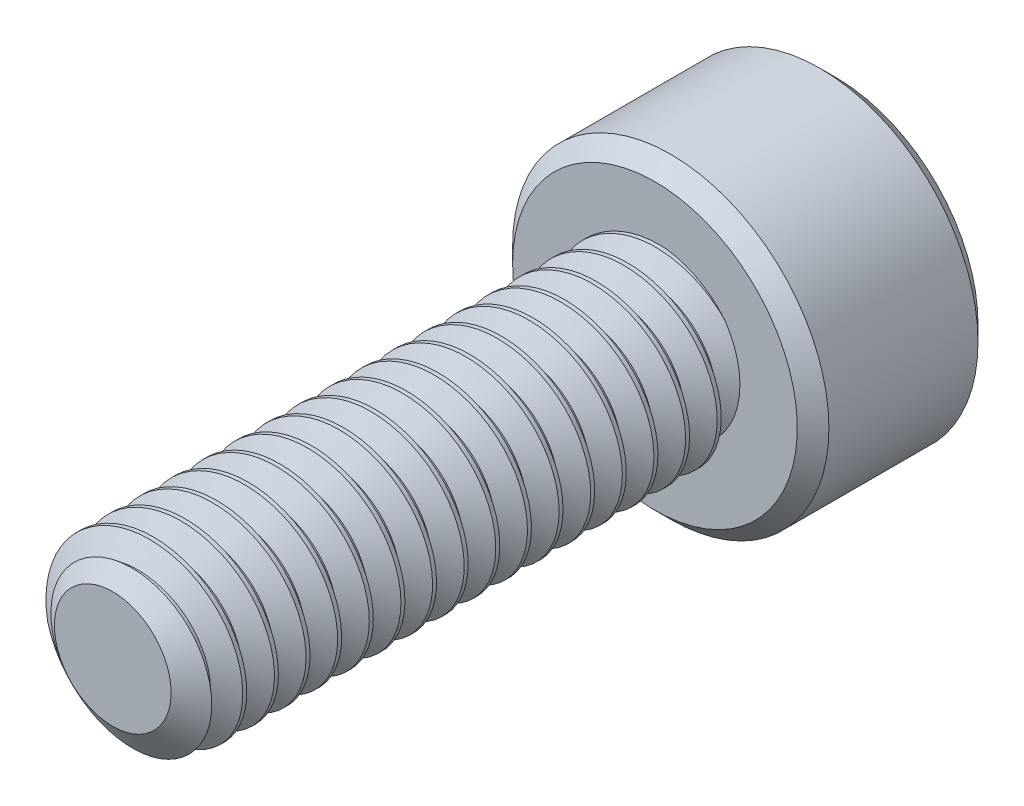
SolidWorks part; units mm, degrees
ref_plane "Front Plane" through (0, 0, 0) normal (0, 0, 1) x (1, 0, 0)
ref_plane "Top Plane" through (0, 0, 0) normal (0, 1, 0) x (1, 0, 0)
ref_plane "Right Plane" through (0, 0, 0) normal (1, 0, 0) x (0, 0, -1)
sketch "Sketch1" plane through (0, 0, 0) normal (0, 0, 1) x (1, 0, 0)
  circle A0 centre (0, 0) radius 2
  dimension "OD" = 4
extrude "Extrude1" add sketch "Sketch1" against normal blind 12
sketch "Sketch2" plane through (0, 0, 0) normal (0, 0, 1) x (1, 0, 0)
  circle A0 centre (0, 0) radius 2 construction
  circle A1 centre (0, 0) radius 2
curve "Helix/Spiral1" pitch 0.7 height 12.7 radius 2 centre (0, 0, 0) axis (0, 0, -1) start towards (0, 1, 0) parameters "pitch"=0.7
sketch "Sketch3" plane through (0, 0, 0) normal (1, 0, 0) x (0, 0, -1)
  line L0 (-0.6125, 2) -> (-0.35, 1.5453)
  line L1 (-0.35, 1.5453) -> (-0.2625, 1.5453)
  line L2 (-0.2625, 1.5453) -> (0, 2)
  line L3 (-0.6125, 2) -> (0, 2)
  line L4 (-0.3062, 2) -> (-0.3062, 1.5453) construction
  line L5 (-0.4812, 1.7727) -> (-0.1312, 1.7727) construction
  line L6 (0, 2) -> (0, -2) construction
  dimension "D1" = 0.0875
  dimension "D2" = 0.35
  dimension "D3" = 60
sweep "Cut-Sweep1" cut profiles "Sketch3" path "Helix/Spiral1"
sketch "Sketch4" plane through (0, 0, 0) normal (1, 0, 0) x (0, 0, -1)
  line L0 (0.4962, 2) -> (0, 1.2913)
  line L1 (0, 1.2913) -> (0, 2)
  line L2 (0.4962, 2) -> (0, 2)
  line L3 (-0.6125, 2) -> (0, 2) construction
  line L4 (0, 0) -> (7.0209, 0) construction
  dimension "D1" = 55
  dimension "D2" = 0.254
revolve "Cut-Revolve1" cut sketch "Sketch4" angle 360 about L4
sketch "Sketch6" plane through (0, 0, -12) normal (0, 0, -1) x (-1, 0, 0)
  circle A0 centre (0, 0) radius 3.5
  dimension "head dia" = 7
extrude "Extrude2" add sketch "Sketch6" along normal blind 4
sketch "Sketch7" plane through (0, 0, -16) normal (0, 0, -1) x (-1, 0, 0)
  line L1 (0, 1.7321) -> (-1.5, 0.866)
  line L2 (-1.5, 0.866) -> (-1.5, -0.866)
  line L3 (-1.5, -0.866) -> (0, -1.7321)
  line L4 (0, -1.7321) -> (1.5, -0.866)
  line L5 (1.5, -0.866) -> (1.5, 0.866)
  line L6 (1.5, 0.866) -> (0, 1.7321)
  circle A0 centre (0, 0) radius 1.5 construction
  dimension "hex dia" = 3
extrude "Cut-Extrude1" cut sketch "Sketch7" against normal blind 2.25
sketch "Sketch8" plane through (0, 0, -16) normal (0, 0, -1) x (-1, 0, 0)
  circle A0 centre (0, 0) radius 1.7321
extrude "Cut-Extrude2" cut sketch "Sketch8" against normal through all draft 45
chamfer "Chamfer1" distance 0.35 angle 45 2 edges at (-3.5, 0, -16) (-3.5, 0, -12)
sketch "Sketch10" plane through (0, 0, -12) normal (0, 0, 1) x (1, 0, 0)
  circle A1 centre (0, 0) radius 2
  circle A2 centre (0, 0) radius 2
  dimension "D1" = 0
ref_plane "Plane1" through (0, 0, 0) normal (0, 0, 1) x (1, 0, 0)
extrude "partial thread" [suppressed] add sketch "Sketch10" along normal up to surface (10 mm away) separate body up to plane "Plane1"
chamfer "Chamfer2" [suppressed] distance 0.08 angle 45
combine bodies "Combine1" [suppressed] operation type add bodies to combine 107 108
sketch "Sketch9" plane through (0, 0, 0) normal (1, 0, 0) x (0, 0, -1)
  line L0 (0, 2) -> (0, -2) construction
  line L1 (1.75, 2) -> (1.75, -2) construction
  dimension "D1" = 1.75
equation "\"D3@Helix/Spiral1\" = \"screw length@Extrude1\"+\"pitch@Helix/Spiral1\""
equation "\"D1@Sketch3\" = \"pitch@Helix/Spiral1\"*.125"
equation "\"D2@Sketch3\" = \"pitch@Helix/Spiral1\"*.5"
equation "\"D1@Cut-Extrude1\" = \"hex dia@Sketch7\"*.75"
equation "\"D1@Chamfer1\" = \"head dia@Sketch6\"*.05"
equation "\"D1@Sketch9\" = \"pitch@Helix/Spiral1\"*2.5"
equation "\"D1@Chamfer2\"=\"OD@Sketch1\"*.02"
